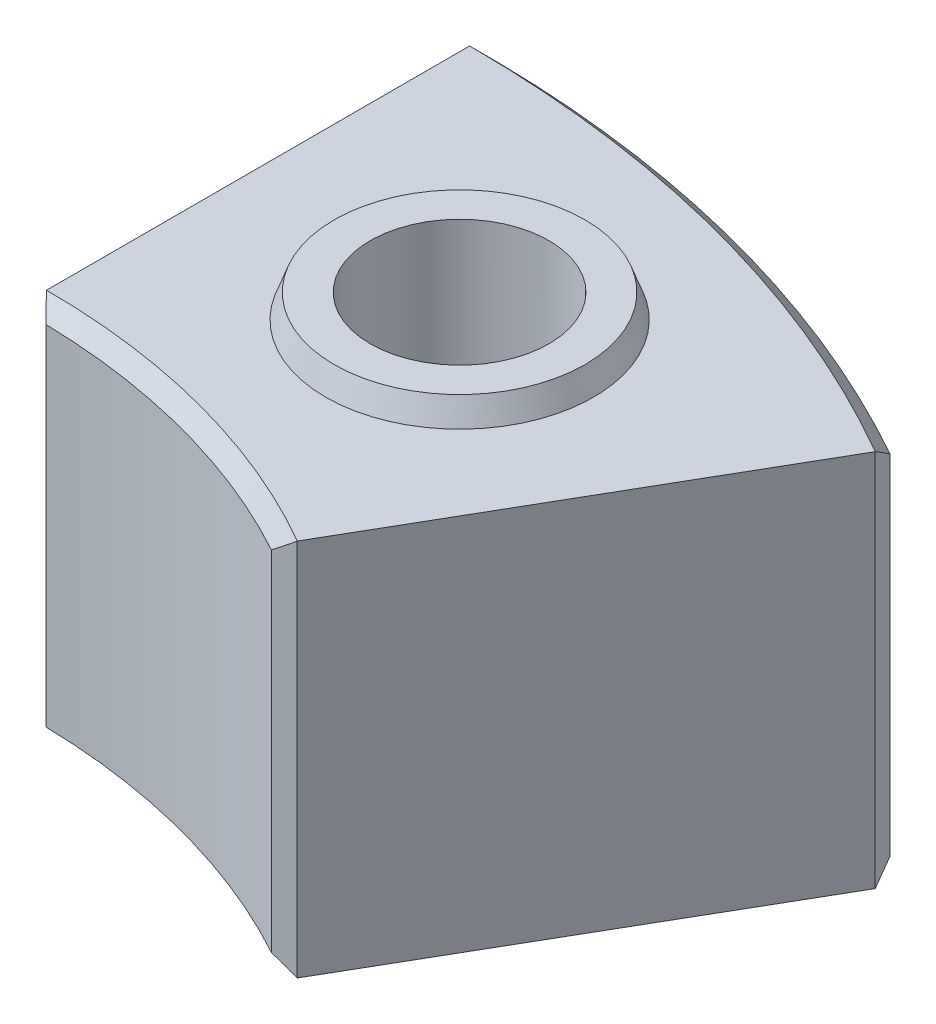
SolidWorks part; units mm, degrees
ref_plane "Front Plane" through (0, 0, 0) normal (0, 0, 1) x (1, 0, 0)
ref_plane "Top Plane" through (0, 0, 0) normal (0, 1, 0) x (1, 0, 0)
ref_plane "Right Plane" through (0, 0, 0) normal (1, 0, 0) x (0, 0, -1)
sketch "Sketch1" plane through (0, 0, 0) normal (0, 1, 0) x (1, 0, 0)
  line L0 (0, 0) -> (0, 50000) construction
  line L1 (112.5, 194.8557) -> (188.5, 326.4916)
  line L10 (0, 225) -> (0, 50225) construction
  line L11 (0, 225) -> (0, 377)
  line L14 (0, 0) -> (25000, 43301.2702) construction
  line L15 (0, 0) -> (12940.9523, 48296.2913) construction
  line L16 (0, 0) -> (35355.3391, 35355.3391) construction
  line L17 (0, 0) -> (48296.2913, 12940.9523) construction
  line L18 (0, 0) -> (50000, 0) construction
  circle A9 centre (77.9045, 290.7437) radius 30
  arc A12 (188.5, 326.4916) -> (0, 377) centre (0, 0) ccw
  arc A13 (150.5, 260.6736) -> (0, 301) centre (0, 0) ccw construction
  arc A14 (112.5, 194.8557) -> (0, 225) centre (0, 0) ccw
  point P2 (0, 0)
  point P6 (0, 0)
  dimension "D1" = 225
  dimension "D2" = 377
  dimension "D4" = 15
  dimension "D5" = 301
  dimension "D7" = 15
  dimension "D6" = 60
  dimension "D3" = 30
  dimension "D8" = 30
extrude "Boss-Extrude1" add sketch "Sketch1" against normal blind 127
sketch "Sketch3" plane through (0, 0, 0) normal (0, 1, 0) x (1, 0, 0)
  circle A0 centre (77.9045, 290.7437) radius 30
  circle A1 centre (77.9045, 290.7437) radius 45
  dimension "D1" = 60
  dimension "D2" = 90
extrude "Boss-Extrude2" add sketch "Sketch3" along normal blind 8
chamfer "Chamfer1" distance 8 angle 20 1 edges at (77.9045, 8, -245.7437)
sketch "Sketch4" plane through (0, -127, 0) normal (0, -1, 0) x (1, 0, 0)
  circle A0 centre (77.9045, -290.7437) radius 46
  circle A1 centre (77.9045, -290.7437) radius 30
  dimension "D1" = 92
  dimension "D2" = 60
extrude "Cut-Extrude1" cut sketch "Sketch4" against normal blind 10
chamfer "Chamfer2" distance 10 angle 20 1 edges at (77.9045, -117, -336.7437)
chamfer "Chamfer3" distance 5 8 edges at (112.5, -63.5, -194.8557) (58.2343, -127, -217.3333) (0, -63.5, -225) (58.2343, 0, -217.3333) (0, -63.5, -377) (97.5748, -127, -364.154) (188.5, -63.5, -326.4916) (97.5748, 0, -364.154)
